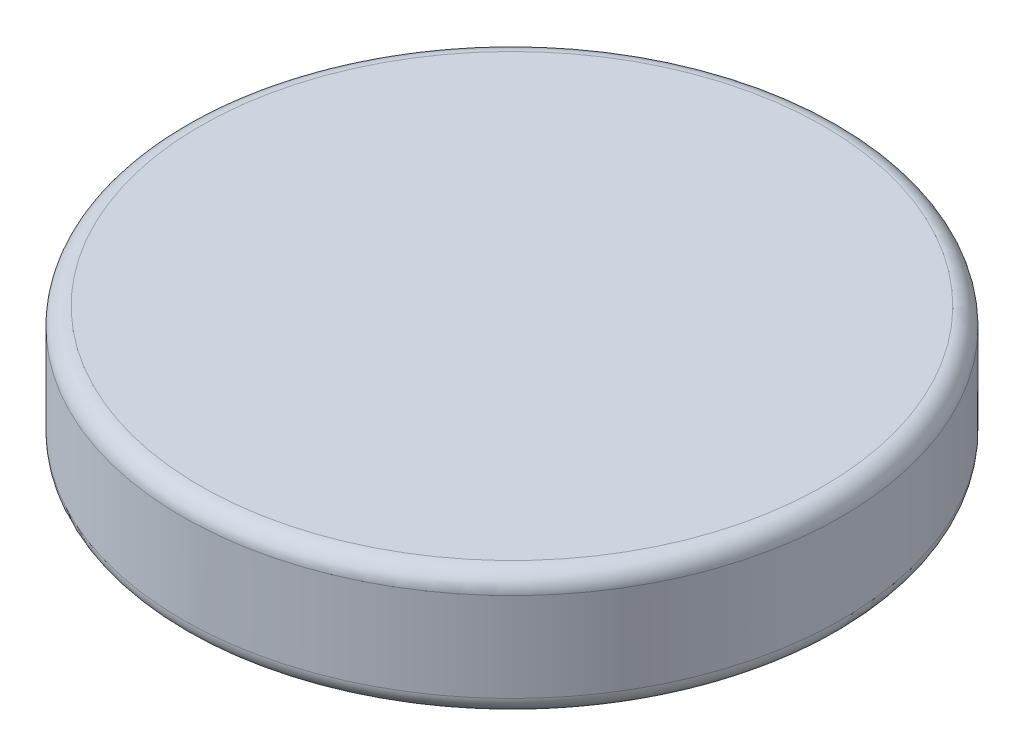
SolidWorks part; units mm, degrees
ref_plane "Front Plane" through (0, 0, 0) normal (0, 0, 1) x (1, 0, 0)
ref_plane "Top Plane" through (0, 0, 0) normal (0, 1, 0) x (1, 0, 0)
ref_plane "Right Plane" through (0, 0, 0) normal (1, 0, 0) x (0, 0, -1)
sketch "Sketch2" plane through (0, 0, 0) normal (0, 0, 1) x (1, 0, 0)
  line L0 (0, 0) -> (0, 5) construction
  line L1 (0, 5) -> (-11, 5) construction
  line L2 (-11, 5) -> (-11, 15) construction
  line L3 (-11, 15) -> (29, 15) construction
  line L4 (29, 15) -> (29, 5) construction
  line L5 (29, 5) -> (18, 5) construction
  line L6 (18, 5) -> (18, 0) construction
  line L7 (18, 0) -> (0, 0) construction
  line L11 (1.5, 1.5) -> (1.5, 5.5)
  line L12 (0.5, 6.5) -> (-9.5, 6.5)
  line L16 (-9.5, 6.5) -> (-9.5, 13.5)
  line L17 (-9.5, 13.5) -> (9, 13.5)
  line L21 (9, 1.5) -> (1.5, 1.5)
  line L22 (9, 1.5) -> (9, 13.5)
  line L23 (1.5, 1.5) -> (1.5, 6.5) construction
  line L24 (1.5, 6.5) -> (-9.5, 6.5) construction
  line L26 (-9.5, 13.5) -> (27.5, 13.5) construction
  line L27 (27.5, 6.5) -> (16.5, 6.5) construction
  line L28 (27.5, 13.5) -> (27.5, 6.5) construction
  line L29 (16.5, 6.5) -> (16.5, 1.5) construction
  line L30 (16.5, 1.5) -> (1.5, 1.5) construction
  arc A1 (1.5, 5.5) -> (0.5, 6.5) centre (0.5, 5.5) ccw
  point P23 (9, 13.5)
  point P24 (9, 1.5)
  dimension "D7" = 18.5
  dimension "D6" = 1
  dimension "D1" = 40
  dimension "D2" = 18
  dimension "D3" = 10
  dimension "D4" = 5
  dimension "D5" = 1.5
revolve "Revolve1" add sketch "Sketch2" angle 360 about L22
sketch "Sketch3" plane through (0, 1.5, 0) normal (0, -1, 0) x (1, 0, 0)
  circle A0 centre (9, 0) radius 4.1416
  circle A1 centre (9, 0) radius 7.5
  circle A2 centre (9, 0) radius 7.5 construction
  dimension "D1" = 0
extrude "Cut-Extrude1" cut sketch "Sketch3" against normal blind 10
fillet "Fillet2" radius 1 2 edges at (9, 13.5, -18.5) (9, 6.5, -18.5)
fillet "Fillet3" radius 1 1 edges at (9, 1.5, -7.5)
